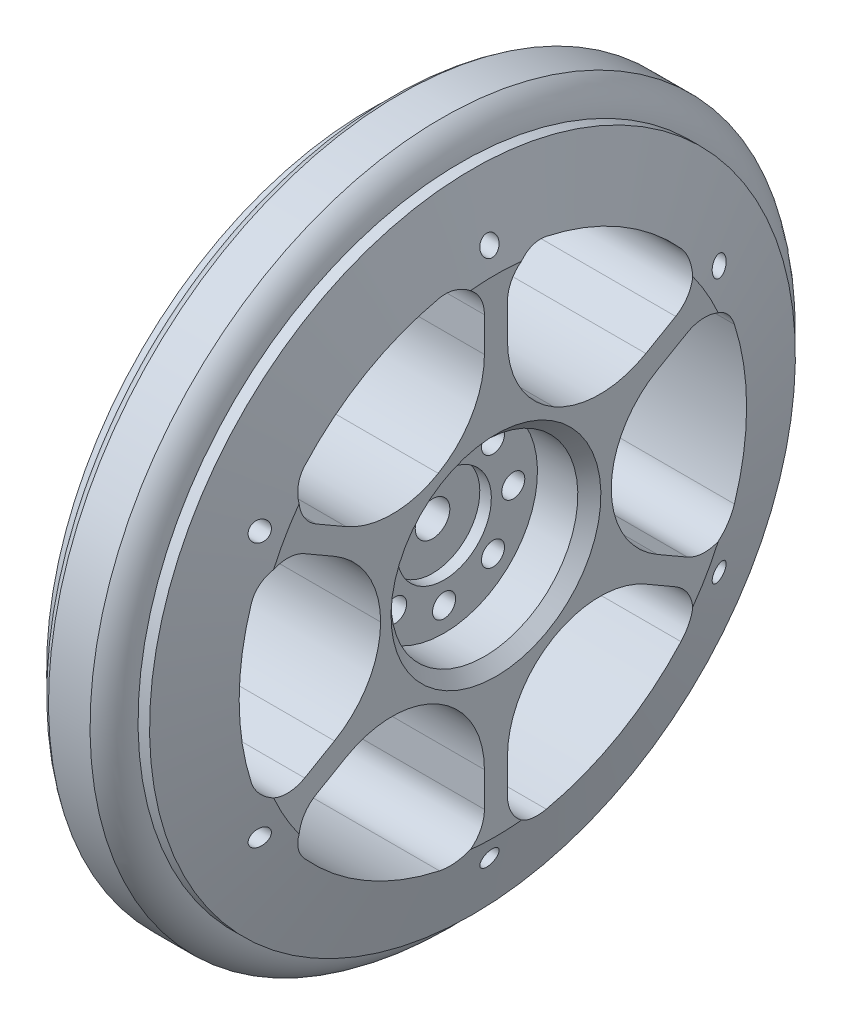
SolidWorks part; units mm, degrees
material "ABS"
ref_plane "Front" through (0, 0, 0) normal (0, 0, 1) x (1, 0, 0)
ref_plane "Top" through (0, 0, 0) normal (0, 1, 0) x (1, 0, 0)
ref_plane "Right" through (0, 0, 0) normal (1, 0, 0) x (0, 0, -1)
sketch "ｽｹｯﾁ1" plane through (0, 0, 0) normal (0, 0, 1) x (1, 0, 0)
  line L0 (-6.5, 8.1) -> (-2, 8.1)
  line L1 (-1, 0) -> (1, 0)
  line L2 (-6.5, 8.1) -> (-6.5, 21.1)
  line L3 (-4.4641, 28) -> (-3.4641, 28)
  line L4 (6.5, 8.1) -> (6.5, 21.1)
  line L5 (-6.6561, 2.2738) -> (6.5, 28) construction
  line L6 (-6.5, 28) -> (1.4647, 12.4253) construction
  line L7 (-2, 8.1) -> (-2, 4.1)
  line L8 (-2, 4.1) -> (-1, 4.1)
  line L9 (-1, 4.1) -> (-1, 0)
  line L10 (1, 0) -> (1, 4.1)
  line L11 (1, 4.1) -> (2, 4.1)
  line L12 (2, 4.1) -> (2, 8.1)
  line L13 (2, 8.1) -> (6.5, 8.1)
  line L14 (-4.4641, 28) -> (-6.5, 21.1)
  line L15 (-6.5, 21.1) -> (6.5, 21.1) construction
  line L16 (6.5, 21.1) -> (4.4641, 28)
  line L17 (3.4641, 28) -> (4.4641, 28)
  line L18 (-1.8028, 30.5) -> (1.8028, 30.5)
  arc A0 (3.4641, 28) -> (1.8028, 30.5) centre (0, 27.5) ccw
  arc A1 (-1.8028, 30.5) -> (-3.4641, 28) centre (0, 27.5) ccw
  point P4 (0, 15.2895)
  point P8 (0, 0)
  dimension "D8" = 7
  dimension "D9" = 27.5
  dimension "D12" = 0
  dimension "D1" = 0
  dimension "D2" = 13
  dimension "D3" = 2
  dimension "D4" = 0
  dimension "D5" = 1
  dimension "D6" = 4.1
  dimension "D7" = 8.1
  dimension "D10" = 1
  dimension "D11" = 1
  dimension "D13" = 13
  dimension "D14" = 28
  dimension "D15" = 30.5
revolve "回転1" add sketch "ｽｹｯﾁ1" angle 360 about L1
sketch "ｽｹｯﾁ2" plane through (-6.5, 0, 0) normal (-1, 0, 0) x (0, 0, 1)
  circle A0 centre (0, 0) radius 1.5
  dimension "D1" = 3
extrude "ｶｯﾄ - 押し出し1" cut sketch "ｽｹｯﾁ2" against normal blind 10
sketch "ｽｹｯﾁ3" plane through (-2, 0, 0) normal (-1, 0, 0) x (0, 0, 1)
  circle A0 centre (0, 6) radius 1
  circle A1 centre (0, 0) radius 1.5 construction
  dimension "D1" = 2
  dimension "D2" = 6
extrude "ｶｯﾄ - 押し出し2" cut sketch "ｽｹｯﾁ3" against normal blind 10
pattern_circular "円形ﾊﾟﾀｰﾝ1" count 8 over 360 about axis through (-1, 0, 0) along (-1, 0, 0) of "ｶｯﾄ - 押し出し2" reverse direction yes
chamfer "面取り1" distance 1 angle 45 2 edges at (6.5, -8.1, 0) (-6.5, -8.1, 0)
sketch "ｽｹｯﾁ4" plane through (6.5, 0, 0) normal (1, 0, 0) x (0, 0, -1)
  line L0 (0, 23) -> (0, 0) construction
  circle A0 centre (0, 23) radius 0.8
  dimension "D1" = 1.6
  dimension "D2" = 23
extrude "ｶｯﾄ - 押し出し3" cut sketch "ｽｹｯﾁ4" against normal through all
pattern_circular "円形ﾊﾟﾀｰﾝ2" count 6 over 360 about axis through (-1, 0, 0) along (-1, 0, 0) of "ｶｯﾄ - 押し出し3" reverse direction yes
sketch "ｽｹｯﾁ5" plane through (6.5, 0, 0) normal (1, 0, 0) x (0, 0, -1)
  line L0 (0, 0) -> (0, 23) construction
  line L1 (0, 0) -> (19.9186, 11.5) construction
  line L2 (1, 21.9773) -> (1, 9.9499)
  line L3 (8.1168, 5.841) -> (18.5329, 11.8547)
  circle A0 centre (0, 0) radius 22
  circle A1 centre (0, 0) radius 10
  circle M7 centre (0, 0) radius 21.1
  dimension "D1" = 44
  dimension "D2" = 20
  dimension "D3" = 1
  dimension "D4" = 1
extrude "ｶｯﾄ - 押し出し4" cut sketch "ｽｹｯﾁ5" against normal through all contours A1 L3 L2 M7 | L3 A0 L2 M7 region at (6.5, 18.8752, -10.8976) region at (6.5, 13.6211, -7.8641)
pattern_circular "円形ﾊﾟﾀｰﾝ3" count 6 over 360 about axis through (-1, 0, 0) along (-1, 0, 0) of "ｶｯﾄ - 押し出し4" reverse direction yes
fillet "ﾌｨﾚｯﾄ1" radius 3 12 edges at (0, -21.9773, 1) (0, -11.8547, 18.5329) (0, 10.1226, 19.5329) (0, 21.9773, 1) (0, 11.8547, 18.5329) (0, -10.1226, 19.5329) (0, -21.9773, -1) (0, -11.8547, -18.5329) (0, -10.1226, -19.5329) (0, 10.1226, -19.5329) (0, 11.8547, -18.5329) (0, 21.9773, -1)
fillet "ﾌｨﾚｯﾄ2" radius 8 12 edges at (0, 4.1089, 9.1168) (0, -4.1089, 9.1168) (0, -5.841, 8.1168) (0, -9.9499, 1) (0, -9.9499, -1) (0, -5.841, -8.1168) (0, -4.1089, -9.1168) (0, 4.1089, -9.1168) (0, 5.841, -8.1168) (0, 9.9499, -1) (0, 9.9499, 1) (0, 5.841, 8.1168)
